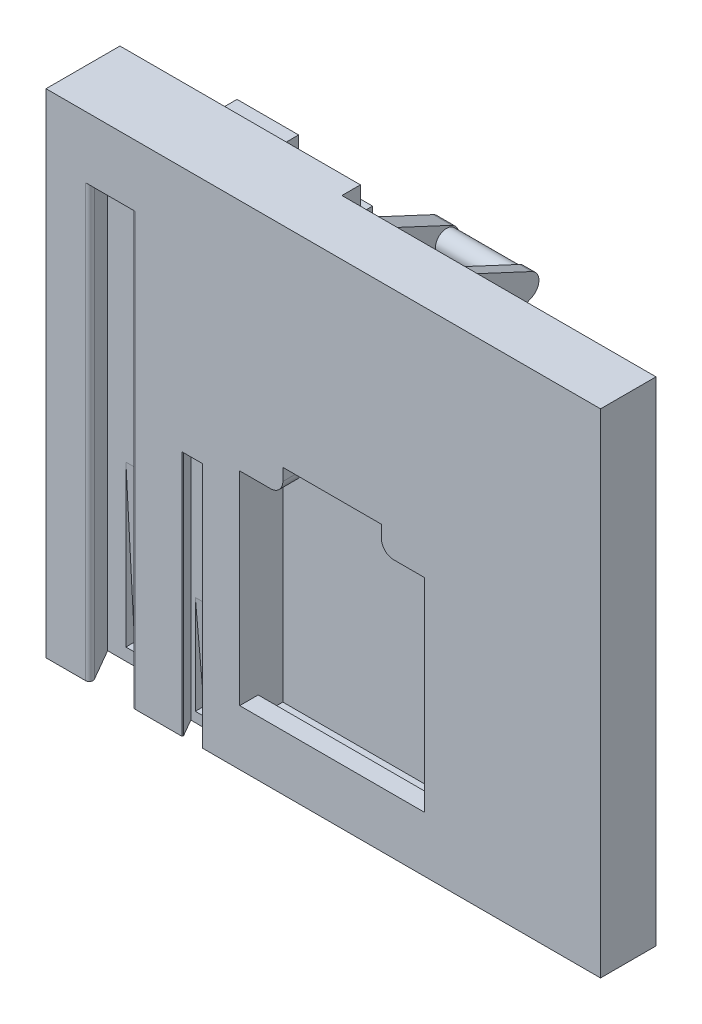
SolidWorks part; units mm, degrees
note: The reader was unsure of these and kept them because the rebuilt part matched: shared geometry of "Sketch15<3>", "Sketch15<4>".
ref_plane "Front Plane" through (0, 0, 0) normal (0, 0, 1) x (1, 0, 0)
ref_plane "Top Plane" through (0, 0, 0) normal (0, 1, 0) x (1, 0, 0)
ref_plane "Right Plane" through (0, 0, 0) normal (1, 0, 0) x (0, 0, -1)
sketch "Sketch1" plane through (0, 0, 0) normal (0, 0, 1) x (1, 0, 0)
  line L0 (22.5, 20) -> (-22.5, -20) construction
  line L1 (-22.5, 20) -> (22.5, 20)
  line L2 (-22.5, 20) -> (-22.5, -20)
  line L3 (-22.5, -20) -> (22.5, -20)
  line L4 (22.5, 20) -> (22.5, -20)
  point P4 (0, 0)
  dimension "D1" = 40
  dimension "D2" = 45
extrude "Boss-Extrude1" add sketch "Sketch1" along normal blind 6
sketch "Sketch2" plane through (0, -20, 0) normal (0, -1, 0) x (1, 0, 0)
  line L0 (-15.7679, 6) -> (-14.0359, 3)
  line L1 (-22.5, 6) -> (22.5, 6) construction
  line L2 (-14.0359, 3) -> (-20.5, 3)
  line L3 (-20.5, 3) -> (-18.7679, 6)
  line L4 (-18.7679, 6) -> (-15.7679, 6)
  line L5 (-22.5, 6) -> (-22.5, 0) construction
  dimension "D1" = 3
  dimension "D2" = 60
  dimension "D3" = 3
  dimension "D4" = 2
extrude "Cut-Extrude1" cut sketch "Sketch2" against normal blind 35
sketch "Sketch3" plane through (0, 0, 3) normal (0, 0, 1) x (1, 0, 0)
  line L0 (-18.5179, -17.5) -> (-16.0179, -17.5) construction
  line L1 (-18.5179, -16.5) -> (-16.0179, -16.5)
  line L2 (-18.5179, -18.5) -> (-16.0179, -18.5)
  line L3 (-20.5, -20) -> (-14.0359, -20) construction
  arc A0 (-18.5179, -16.5) -> (-18.5179, -18.5) centre (-18.5179, -17.5) ccw
  arc A1 (-16.0179, -18.5) -> (-16.0179, -16.5) centre (-16.0179, -17.5) ccw
  point P2 (-17.2679, -17.5)
  point P9 (-17.2679, -20)
  dimension "D1" = 2
  dimension "D2" = 2.5
  dimension "D3" = 1.5
extrude "Cut-Extrude2" [suppressed] cut sketch "Sketch3" against normal blind 2
fillet "Fillet3" [suppressed] radius 1
fillet "Fillet4" radius 0.3 2 edges at (-15.7679, -2.5, 6) (-18.7679, -2.5, 6)
sketch "Sketch5" plane through (0, -20, 0) normal (0, -1, 0) x (1, 0, 0)
  line L0 (-9.8823, 6) -> (-9.0163, 4.5)
  line L1 (-9.0163, 4.5) -> (-12.2483, 4.5)
  line L2 (-12.2483, 4.5) -> (-11.3823, 6)
  line L3 (-11.3823, 6) -> (-9.8823, 6)
  line L4 (-15.2483, 6) -> (22.5, 6) construction
  dimension "D1" = 1.5
  dimension "D2" = 60
  dimension "D3" = 1.5
  dimension "D4" = 3
extrude "Cut-Extrude4" cut sketch "Sketch5" against normal blind 20
chamfer "Chamfer1" distance 0.1 distance2 0.1 2 edges at (-9.8823, -10, 6) (-11.3823, -10, 6)
sketch "Sketch6" plane through (0, 0, 4.5) normal (0, 0, 1) x (1, 0, 0)
  line L0 (-11.1323, -17.7) -> (-10.1323, -17.7) construction
  line L1 (-11.1323, -16.9) -> (-10.1323, -16.9)
  line L2 (-11.1323, -18.5) -> (-10.1323, -18.5)
  line L3 (-12.2483, -20) -> (-9.0163, -20) construction
  arc A0 (-11.1323, -16.9) -> (-11.1323, -18.5) centre (-11.1323, -17.7) ccw
  arc A1 (-10.1323, -18.5) -> (-10.1323, -16.9) centre (-10.1323, -17.7) ccw
  point P2 (-10.6323, -17.7)
  point P9 (-10.6323, -20)
  dimension "D1" = 0.8
  dimension "D2" = 1
  dimension "D3" = 1.5
extrude "Cut-Extrude5" [suppressed] cut sketch "Sketch6" against normal blind 1.5
sketch "Sketch7" plane through (0, -20, 0) normal (0, -1, 0) x (1, 0, 0)
  line L0 (-2.4389, 6) -> (-1.8616, 5)
  line L1 (-1.8616, 5) -> (-4.0163, 5)
  line L2 (-4.0163, 5) -> (-3.4389, 6)
  line L3 (-3.4389, 6) -> (-2.4389, 6)
  line L4 (-9.7823, 6) -> (22.5, 6) construction
  dimension "D1" = 1
  dimension "D2" = 60
  dimension "D3" = 5
  dimension "D4" = 1
extrude "Cut-Extrude6" [suppressed] cut sketch "Sketch7" against normal blind 20
sketch "Sketch8" [suppressed] plane through (0, 0, 5) normal (0, 0, 1) x (1, 0, 0)
  line L0 (7.0611, -19) -> (7.0611, -17.4891) construction
  line L1 (6.4111, -19) -> (7.7111, -19)
  line L2 (6.4111, -19) -> (6.4111, -16)
  line L3 (6.4111, -16) -> (7.7111, -16)
  line L4 (7.7111, -19) -> (7.7111, -16)
  line L5 (5.9837, -20) -> (8.1384, -20) construction
  point P9 (7.0611, -20)
  dimension "D1" = 1
  dimension "D2" = 3
  dimension "D3" = 1.3
extrude "Cut-Extrude7" [suppressed] cut sketch "Sketch8" against normal blind 0.5
sketch "Sketch10" plane through (0, -20, 0) normal (0, -1, 0) x (1, 0, 0)
  line L1 (22.5, 0) -> (-2.9878, 0)
  line L2 (22.5, 0) -> (22.5, 1.5)
  line L3 (22.5, 1.5) -> (-2.9878, 1.5)
  line L4 (-2.9878, 0) -> (-2.9878, 1.5)
  dimension "D1" = 1.5
extrude "Cut-Extrude8" cut sketch "Sketch10" against normal through all
ref_plane "Plane1" through (-17.2679, 0, 0) normal (1, 0, 0) x (0, 0, -1)
sketch "Sketch11" plane through (-17.2679, 0, 0) normal (1, 0, 0) x (0, 0, -1)
  line L0 (-3, -19) -> (-3, -6)
  line L1 (-3, 15) -> (-3, -20) construction
  line L2 (-3, -6) -> (-2.3, -19)
  line L3 (-2.3, -19) -> (-3, -19)
  line L4 (-6, -20) -> (0, -20) construction
  dimension "D1" = 1
  dimension "D2" = 0.7
  dimension "D3" = 13
  dimension "D4" = 3.082
extrude "Cut-Extrude9" cut sketch "Sketch11" against normal mid plane 3.5
ref_plane "Plane2" through (-10.6323, 0, 0) normal (1, 0, 0) x (0, 0, -1)
sketch "Sketch12" plane through (-10.6323, 0, 0) normal (1, 0, 0) x (0, 0, -1)
  line L0 (-4.5, -19.2) -> (-4.5, -11.199)
  line L1 (-4.5, 0) -> (-4.5, -20) construction
  line L2 (-4.5, -11.199) -> (-3.8, -19.2)
  line L3 (-3.8, -19.2) -> (-4.5, -19.2)
  line L4 (-3, -20) -> (-5.55, -20) construction
  dimension "D1" = 5
  dimension "D2" = 0.8
  dimension "D3" = 0.7
extrude "Cut-Extrude10" cut sketch "Sketch12" against normal mid plane 2.5
sketch "Sketch13" plane through (0, 0, 6) normal (0, 0, 1) x (1, 0, 0)
  line L0 (-9.7823, -20) -> (22.5, -20) construction
  line L1 (8.2177, -17) -> (-6.7823, -17)
  line L2 (8.2177, -17) -> (8.2177, 3)
  line L3 (8.2177, 3) -> (-6.7823, 3)
  line L4 (-6.7823, -17) -> (-6.7823, 3)
  line L5 (-9.7823, 0) -> (-9.7823, -20) construction
  dimension "D1" = 15
  dimension "D2" = 20
  dimension "D3" = 3
  dimension "D4" = 3
extrude "Cut-Extrude11" cut sketch "Sketch13" against normal blind 3.5
sketch "Sketch14" plane through (0, 0, 6) normal (0, 0, 1) x (1, 0, 0)
  line L0 (8.2177, -17) -> (8.2177, 3) construction
  line L1 (-6.7823, -17) -> (8.2177, -17)
  line L2 (-6.7823, -17) -> (-6.7823, -15.5)
  line L3 (-6.7823, -15.5) -> (8.2177, -15.5)
  line L4 (8.2177, -17) -> (8.2177, -15.5)
  line L6 (-6.7823, 3) -> (-3.2823, 3)
  line L7 (-6.7823, 3) -> (-6.7823, 1)
  line L8 (-6.7823, 1) -> (-3.2823, 1)
  line L9 (-3.2823, 3) -> (-3.2823, 1)
  line L10 (8.2177, 3) -> (4.7177, 3)
  line L11 (8.2177, 3) -> (8.2177, 1)
  line L12 (8.2177, 1) -> (4.7177, 1)
  line L13 (4.7177, 3) -> (4.7177, 1)
  dimension "D1" = 3.5
  dimension "D2" = 2
  dimension "D3" = 1.5
extrude "Boss-Extrude2" add sketch "Sketch14" against normal blind 1.5
fillet "Fillet5" radius 1 2 edges at (-3.2823, 1, 5.25) (4.7177, 1, 5.25)
sketch "Sketch4" plane through (0, 0, 0) normal (0, 0, -1) x (-1, 0, 0)
  text T0 "60deg 3mm SPAN 3mm dEPTH 0.3FILLET" font "Century Gothic" height 1
sketch "Sketch15" plane through (0, 0, 0) normal (1, 0, 0) x (0, 0, -1)
  line L0 (-6, 20) -> (-1.5, 20) construction
  line L2 (2.5, -2.9686) -> (1.3741, -3.369) construction
  line L3 (-1.5, 0) -> (2.9226, -2.0623)
  line L4 (2.9226, -3.8749) -> (-1.5, -5.9372)
  line L5 (-15.2957, 7.0314) -> (5.2623, 7.0314) construction
  line L6 (-1.5, 0) -> (-1.5, -5.9372)
  line L7 (2.9226, -2.0623) -> (-1.5, 0)
  line L8 (-1.5, -5.9372) -> (2.9226, -3.8749)
  line L15 (2.5, 17.0314) -> (1.3741, 17.4318) construction
  line L16 (-1.5, 20) -> (2.9226, 17.9377)
  line L17 (2.9226, 16.1251) -> (-1.5, 14.0628)
  line L18 (-1.5, 14.0628) -> (-1.5, 20)
  line L19 (2.9226, 17.9377) -> (-1.5, 20)
  line L20 (-1.5, 14.0628) -> (2.9226, 16.1251)
  line L21 (-1.5, 20) -> (-1.5, -20) construction
  arc A0 (2.9226, -2.0623) -> (2.9226, -3.8749) centre (2.5, -2.9686) cw
  circle A1 centre (2.5, -2.9686) radius 0.9
  circle A4 centre (2.5, 17.0314) radius 0.9
  arc A5 (2.9226, 16.1251) -> (2.9226, 17.9377) centre (2.5, 17.0314) ccw
  dimension "D7" = 1
  dimension "D8" = 1.8
  dimension "D1" = 20
  dimension "D6" = 50
  dimension "D9" = 5
extrude "Boss-Extrude3" add sketch "Sketch15" along normal blind 1.5 contours L17 A5 L16 L18 A4 | A0 L3 L6 L4 A1
extrude "Boss-Extrude4" add sketch "Sketch15<3>" along normal blind 1 from offset 7 contours A0 L3 L6 L4 A1 | L17 A5 L16 L18 A4
sketch "Sketch15<3>" plane through (0, 0, 0) normal (1, 0, 0) x (0, 0, -1) same geometry as "Sketch15"
extrude "Boss-Extrude5" add sketch "Sketch15<4>" along normal up to surface (8 mm away) contours A4 | A1 up to face at (8, 17.0314, -3.4)
sketch "Sketch15<4>" plane through (0, 0, 0) normal (1, 0, 0) x (0, 0, -1) same geometry as "Sketch15"
sketch "Sketch16" plane through (0, 20, 0) normal (0, 1, 0) x (1, 0, 0)
  line L0 (-21, 1) -> (-21, 2)
  line L1 (-2.9878, 0) -> (-22.5, 0) construction
  line L2 (-21, 2) -> (-18.5, 2)
  line L3 (-18.5, 2) -> (-18.5, 1)
  line L4 (-18.5, 1) -> (-20, 1)
  line L5 (-20, 1) -> (-20, 0)
  line L6 (-20, 0) -> (-22, 0)
  line L7 (-12.5, 2.3708) -> (-12.5, -0.4619) construction
  line L8 (-22, 0) -> (-22.5, 0) construction
  line L9 (-22.5, -6) -> (-22.5, 0) construction
  line L10 (-5, 0) -> (-3, 0)
  line L11 (-5, 1) -> (-5, 0)
  line L12 (-6.5, 1) -> (-5, 1)
  line L13 (-6.5, 2) -> (-6.5, 1)
  line L14 (-4, 2) -> (-6.5, 2)
  line L15 (-4, 1) -> (-4, 2)
  arc A0 (-21, 1) -> (-22, 0) centre (-22, 1) cw
  arc A1 (-4, 1) -> (-3, 0) centre (-3, 1) ccw
  point P15 (-21, 0)
  point P24 (-4, 0)
  dimension "D1" = 1
  dimension "D2" = 1
  dimension "D3" = 1
  dimension "D4" = 1
  dimension "D5" = 2.5
  dimension "D6" = 1.5
  dimension "D7" = 15
extrude "Boss-Extrude6" add sketch "Sketch16" against normal blind 20 from offset 3
ref_plane "Plane3" through (-12.5, 0, 0) normal (1, 0, 0) x (0, 0, -1)
sketch "Sketch18" plane through (-12.5, 0, 0) normal (1, 0, 0) x (0, 0, 1)
  line L0 (-1, -19) -> (-2, -19)
  line L1 (0, -20) -> (0, 20) construction
  line L2 (-2, -19) -> (-2, -17)
  line L3 (-2, -17) -> (-1, -17)
  line L4 (-1, -17) -> (-1, -18)
  line L5 (-1, -18) -> (0, -18)
  line L6 (0, -18) -> (0, -20)
  line L7 (6, -20) -> (0, -20) construction
  arc A0 (-1, -19) -> (0, -20) centre (-1, -20) cw
  point P15 (-14.5958, -0.4153)
  dimension "D1" = 1
  dimension "D2" = 1
  dimension "D3" = 1
  dimension "D4" = 1
  dimension "D5" = 1
extrude "Boss-Extrude7" add sketch "Sketch18" along normal mid plane 5
sketch "Sketch19" plane through (-12.5, 0, 0) normal (1, 0, 0) x (0, 0, -1)
  line L0 (1, 18) -> (1, 17) construction
  line L1 (0, -7.5) -> (1, -7.5)
  line L2 (0, -7.5) -> (0, -8.5)
  line L3 (0, -8.5) -> (1, -8.5)
  line L4 (1, -7.5) -> (1, -8.5) construction
  arc A0 (1, -8.5) -> (1, -7.5) centre (1, -8) ccw
  point P6 (1, 17.5)
  dimension "D1" = 1
  dimension "D2" = 25
extrude "Boss-Extrude8" add sketch "Sketch19" along normal mid plane 10
